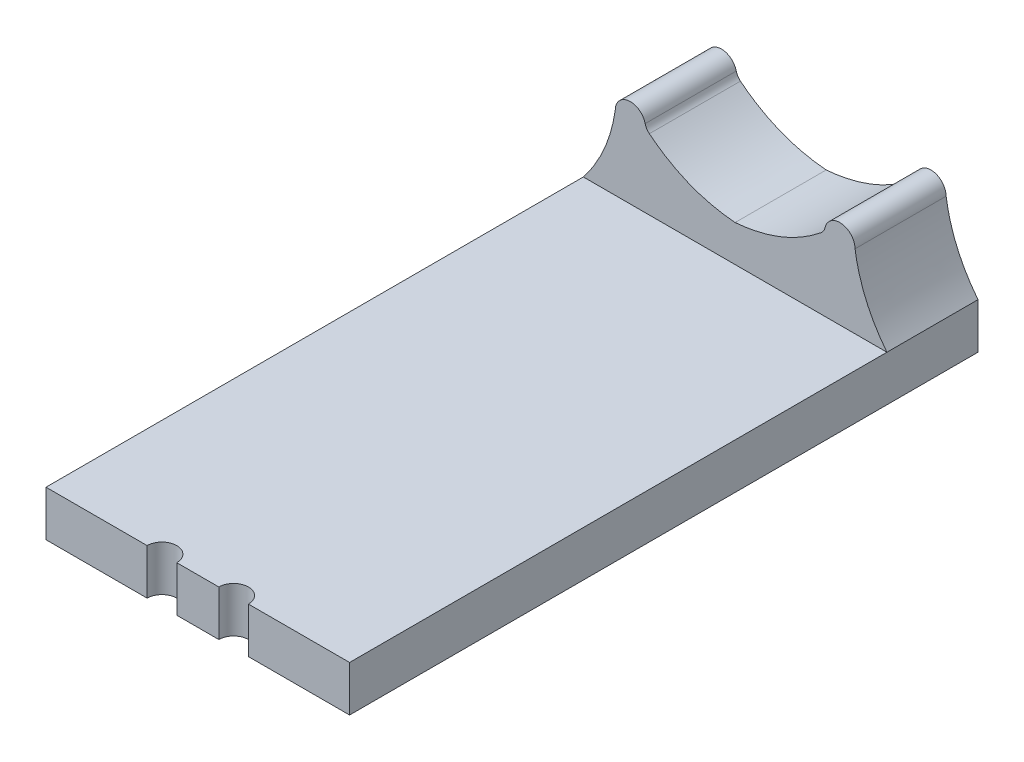
SolidWorks part; units mm, degrees
ref_plane "Front Plane" through (0, 0, 0) normal (0, 0, 1) x (1, 0, 0)
ref_plane "Top Plane" through (0, 0, 0) normal (0, 1, 0) x (1, 0, 0)
ref_plane "Right Plane" through (0, 0, 0) normal (1, 0, 0) x (0, 0, -1)
sketch "Sketch1" plane through (0, 0, 0) normal (0, 0, 1) x (1, 0, 0)
  line L0 (-996.8903, -40.64) -> (49003.1097, -40.64) construction
  line L1 (0, -1000) -> (0, 49000) construction
  line L2 (0, 0) -> (-23.4635, -40.64) construction
  line L3 (0, 0) -> (-40.64, -40.64) construction
  line L4 (-31.75, -53.34) -> (-31.75, -62.865)
  line L5 (-31.75, -62.865) -> (31.75, -62.865)
  line L6 (31.75, -53.34) -> (31.75, -62.865)
  line L7 (-957.5735, -46.99) -> (49042.4265, -46.99) construction
  circle A0 centre (0, 0) radius 40.64 construction
  arc A1 (-18.7325, -37.9449) -> (-25.0825, -37.9449) centre (-21.9075, -37.9449) ccw
  arc A2 (18.7325, -37.9449) -> (25.0825, -37.9449) centre (21.9075, -37.9449) cw
  spline S0 degree 2 poles (-18.7325, -37.9449) (-10.6333, -44.8669) (0, -45.72) knots 0 0 0 1 1 1
  spline S1 degree 2 poles (-25.0825, -37.9449) (-26.3403, -46.4785) (-31.75, -53.34) knots 0 0 0 1 1 1
  spline S2 degree 2 poles (25.0825, -37.9449) (26.3403, -46.4785) (31.75, -53.34) knots 0 0 0 1 1 1
  spline S3 degree 2 poles (18.7325, -37.9449) (10.6333, -44.8669) (0, -45.72) knots 0 0 0 1 1 1
  point P13 (0, -62.865)
  dimension "D1" = 81.28
  dimension "D3" = 6.35
  dimension "D5" = 5.08
  dimension "D2" = 30
  dimension "D4" = 45
  dimension "D6" = 31.75
  dimension "D7" = 9.525
  dimension "D8" = 12.7
  dimension "D9" = 6.35
extrude "Boss-Extrude1" add sketch "Sketch1" along normal mid plane 19.05
sketch "Sketch2" plane through (0, 0, 0) normal (0, 0, 1) x (1, 0, 0)
  line L1 (-31.75, -53.34) -> (31.75, -53.34)
  line L2 (-31.75, -53.34) -> (-31.75, -62.865)
  line L3 (-31.75, -62.865) -> (31.75, -62.865)
  line L4 (31.75, -53.34) -> (31.75, -62.865)
extrude "Boss-Extrude2" add sketch "Sketch2" along normal blind 121.92
fillet "Fillet2" radius 2.54 2 edges at (18.7325, -37.9449, 0) (-18.7325, -37.9449, 0)
sketch "Sketch3" plane through (0, -53.34, 0) normal (0, 1, 0) x (1, 0, 0)
  line L0 (31.75, -121.92) -> (-31.75, -121.92) construction
  line L1 (0, -9.525) -> (0, 9.525) construction
  circle A0 centre (7.5, -121.92) radius 3.1
  circle A1 centre (-7.5, -121.92) radius 3.1
  dimension "D1" = 6.2
  dimension "D2" = 7.5
extrude "Cut-Extrude1" cut sketch "Sketch3" against normal through all
